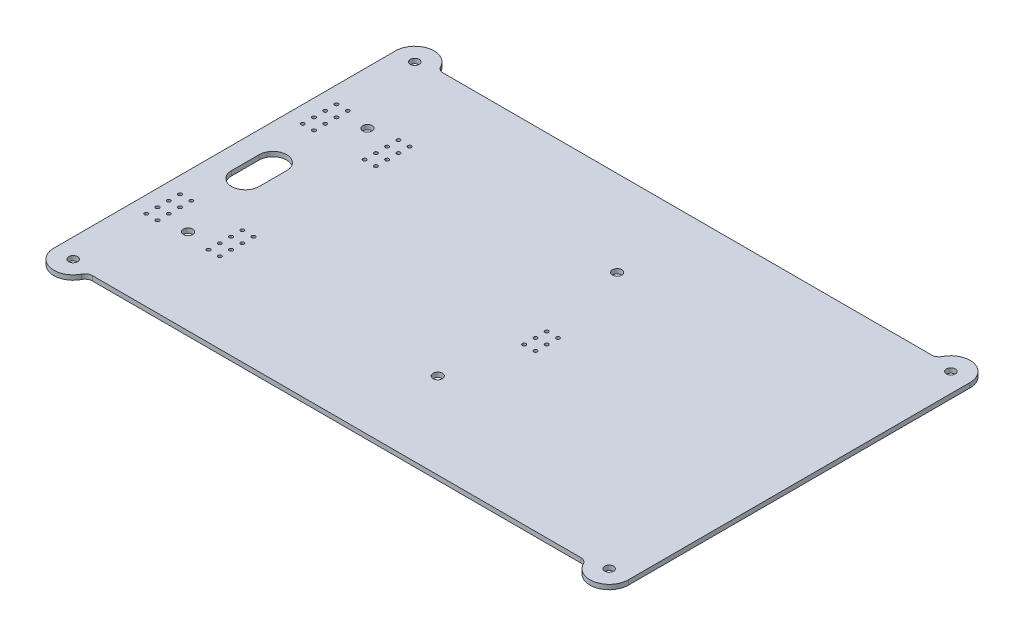
SolidWorks part; units mm, degrees
material "A-Glass Fiber"
ref_plane "Front Plane" through (0, 0, 0) normal (0, 0, 1) x (1, 0, 0)
ref_plane "Top Plane" through (0, 0, 0) normal (0, 1, 0) x (1, 0, 0)
ref_plane "Right Plane" through (0, 0, 0) normal (1, 0, 0) x (0, 0, -1)
sketch "Sketch1" plane through (0, 0, 0) normal (0, 1, 0) x (1, 0, 0)
  line L0 (0, 0) -> (135.8225, 0) construction
  line L2 (-58.612, -57.8231) -> (-58.612, 57.8231)
  line L4 (135.8225, -57.8231) -> (135.8225, 57.8231)
  line L7 (135.8225, 57.9501) -> (135.8225, 66.8401) construction
  line L8 (-44.0467, 59.3713) -> (121.2573, 59.3713)
  line L9 (-44.0467, -59.3713) -> (121.2573, -59.3713)
  arc A0 (-58.612, 57.8231) -> (-46.3123, 60.7627) centre (-52.1108, 57.8231) cw
  arc A1 (123.5228, 60.7627) -> (135.8225, 57.8231) centre (129.3214, 57.8231) cw
  arc A2 (135.8225, -57.8231) -> (123.5228, -60.7627) centre (129.3214, -57.8231) cw
  arc A3 (-46.3123, -60.7627) -> (-58.612, -57.8231) centre (-52.1108, -57.8231) cw
  arc A4 (-46.3123, -60.7627) -> (-44.0467, -59.3713) centre (-44.0467, -61.9113) cw
  arc A5 (121.2573, -59.3713) -> (123.5228, -60.7627) centre (121.2573, -61.9113) cw
  arc A6 (123.5228, 60.7627) -> (121.2573, 59.3713) centre (121.2573, 61.9113) cw
  arc A7 (-44.0467, 59.3713) -> (-46.3123, 60.7627) centre (-44.0467, 61.9113) cw
  arc A8 (31.0353, 66.8607) -> (46.1753, 66.8607) centre (38.6053, 66.9417) ccw construction
  circle A9 centre (-52.1108, -57.8231) radius 3.8735 construction
  circle A10 centre (129.3214, 57.8231) radius 3.8735 construction
  circle A11 centre (-52.1108, 57.8231) radius 3.8735 construction
  circle A12 centre (129.3214, -57.8231) radius 3.8735 construction
  point P1 (0, 0)
  dimension "D1" = 2.54
extrude "Boss-Extrude1" add sketch "Sketch1" against normal blind 1.5875
sketch "Sketch2" plane through (0, 0, 0) normal (0, 1, 0) x (1, 0, 0)
  circle A35 centre (-40.6725, -30.35) radius 1.5875
  circle A36 centre (-40.6725, -30.35) radius 1.5875
  circle A37 centre (-40.6725, 30.35) radius 1.5875
  circle A38 centre (-40.6725, 30.35) radius 1.5875
  circle A39 centre (43.8275, 30.35) radius 1.5875
  circle A40 centre (43.8275, 30.35) radius 1.5875
  circle A41 centre (43.8275, -30.35) radius 1.5875
  circle A42 centre (43.8275, -30.35) radius 1.5875
  dimension "D27" = 0
  dimension "D28" = 0
  dimension "D29" = 0
  dimension "D30" = 0
extrude "Cut-Extrude1" cut sketch "Sketch2" against normal through all
sketch "Sketch3" plane through (0, 0, 0) normal (0, 1, 0) x (1, 0, 0)
  line L5 (-46.6035, 4.285) -> (-46.6035, -5.035) construction
  line L6 (-41.9335, 4.285) -> (-41.9335, -5.035)
  line L7 (-51.2735, 4.285) -> (-51.2735, -5.035)
  line L17 (-43.2035, 3.375) -> (-41.9335, 3.375) construction
  line L18 (-44.8535, 7.2) -> (-44.1998, 8.2889) construction
  line L19 (-46.6035, 7.2) -> (-46.6035, 8.955) construction
  line L20 (-44.8535, 7.2) -> (-48.3535, 7.2) construction
  line L21 (-46.6035, -7.95) -> (-46.6035, -9.705) construction
  line L22 (-48.3535, -7.95) -> (-44.8535, -7.95) construction
  arc A13 (-41.9335, 4.285) -> (-51.2735, 4.285) centre (-46.6035, 4.285) ccw
  arc A14 (-51.2735, -5.035) -> (-41.9335, -5.035) centre (-46.6035, -5.035) ccw
  arc A17 (-44.8535, 0.46) -> (-44.8535, 6.29) centre (-46.6035, 3.375) ccw construction
  point P2 (-46.6035, -0.375)
  dimension "D1" = 1.27
extrude "Cut-Extrude2" cut sketch "Sketch3" against normal through all
sketch "Sketch4" plane through (0, -1.5875, 0) normal (0, -1, 0) x (1, 0, 0)
  line L4 (-34.35, -10.348) -> (-39.27, -10.348)
  line L5 (-34.35, -25.08) -> (-34.35, -10.348)
  line L6 (-39.27, -25.08) -> (-34.35, -25.08)
  line L7 (-39.27, -10.348) -> (-39.27, -25.08)
  line L8 (-34.35, -10.348) -> (-39.27, -10.348)
  line L9 (-34.35, -25.08) -> (-34.35, -10.348)
  line L10 (-39.27, -25.08) -> (-34.35, -25.08)
  line L11 (-39.27, -10.348) -> (-39.27, -25.08)
  line L12 (-34.35, 25.63) -> (-39.27, 25.63)
  line L13 (-34.35, 10.898) -> (-34.35, 25.63)
  line L14 (-39.27, 10.898) -> (-34.35, 10.898)
  line L15 (-39.27, 25.63) -> (-39.27, 10.898)
  line L16 (-34.35, 25.63) -> (-39.27, 25.63)
  line L17 (-34.35, 10.898) -> (-34.35, 25.63)
  line L18 (-39.27, 10.898) -> (-34.35, 10.898)
  line L19 (-39.27, 25.63) -> (-39.27, 10.898)
  line L20 (-44.42, 10.898) -> (-39.5, 10.898)
  line L21 (-39.5, 10.898) -> (-39.5, 25.63)
  line L22 (-39.5, 25.63) -> (-44.42, 25.63)
  line L23 (-44.42, 25.63) -> (-44.42, 10.898)
  line L24 (-44.42, 10.898) -> (-39.5, 10.898)
  line L25 (-39.5, 10.898) -> (-39.5, 25.63)
  line L26 (-39.5, 25.63) -> (-44.42, 25.63)
  line L27 (-44.42, 25.63) -> (-44.42, 10.898)
  line L28 (-39.5, -10.348) -> (-44.42, -10.348)
  line L29 (-39.5, -25.08) -> (-39.5, -10.348)
  line L30 (-44.42, -25.08) -> (-39.5, -25.08)
  line L31 (-44.42, -10.348) -> (-44.42, -25.08)
  line L32 (-39.5, -10.348) -> (-44.42, -10.348)
  line L33 (-39.5, -25.08) -> (-39.5, -10.348)
  line L34 (-44.42, -25.08) -> (-39.5, -25.08)
  line L35 (-44.42, -10.348) -> (-44.42, -25.08)
  line L36 (35.46, 13.148) -> (40.38, 13.148)
  line L37 (35.46, 27.88) -> (35.46, 13.148)
  line L38 (40.38, 27.88) -> (35.46, 27.88)
  line L39 (40.38, 13.148) -> (40.38, 27.88)
  line L40 (35.46, 13.148) -> (40.38, 13.148)
  line L41 (35.46, 27.88) -> (35.46, 13.148)
  line L42 (40.38, 27.88) -> (35.46, 27.88)
  line L43 (40.38, 13.148) -> (40.38, 27.88)
  dimension "D1" = 0
  dimension "D2" = 0
  dimension "D3" = 0
  dimension "D4" = 0
  dimension "D5" = 0
sketch "Sketch6" plane through (0, -1.5875, 0) normal (0, -1, 0) x (1, 0, 0)
  line L0 (-20.19, 27.65) -> (-20.19, 33.65) construction
  line L1 (-20.19, 33.65) -> (-14.19, 33.65) construction
  line L2 (-14.19, 33.65) -> (-14.19, 27.65) construction
  line L3 (-14.19, 27.65) -> (-20.19, 27.65) construction
  line L4 (33.69, -6.45) -> (33.69, -22.45)
  line L5 (54.59, -6.45) -> (33.69, -6.45)
  line L6 (54.59, -22.45) -> (54.59, -6.45)
  line L7 (33.69, -22.45) -> (54.59, -22.45)
  line L8 (33.69, -6.45) -> (33.69, -22.45)
  line L9 (54.59, -6.45) -> (33.69, -6.45)
  line L10 (54.59, -22.45) -> (54.59, -6.45)
  line L11 (33.69, -22.45) -> (54.59, -22.45)
  line L20 (-8.69, 27.65) -> (-8.69, 33.65) construction
  line L21 (-8.69, 33.65) -> (-2.69, 33.65) construction
  line L22 (-2.69, 33.65) -> (-2.69, 27.65) construction
  line L23 (-2.69, 27.65) -> (-8.69, 27.65) construction
  line L24 (-20.19, 27.65) -> (-20.19, 33.65)
  line L25 (-20.19, 33.65) -> (-14.19, 33.65)
  line L26 (-14.19, 33.65) -> (-14.19, 27.65)
  line L27 (-14.19, 27.65) -> (-20.19, 27.65)
  line L28 (-8.69, 27.65) -> (-8.69, 33.65)
  line L29 (-8.69, 33.65) -> (-2.69, 33.65)
  line L30 (-2.69, 33.65) -> (-2.69, 27.65)
  line L31 (-2.69, 27.65) -> (-8.69, 27.65)
  line L80 (55.31, -35.15) -> (55.31, 35.15)
  line L82 (55.31, 35.15) -> (-55.31, 35.15)
  line L84 (-55.31, 35.15) -> (-55.31, -35.15)
  line L86 (-55.31, -35.15) -> (55.31, -35.15)
  line L92 (55.31, -35.15) -> (55.31, 35.15)
  line L94 (55.31, 35.15) -> (-55.31, 35.15)
  line L96 (-55.31, 35.15) -> (-55.31, -35.15)
  line L98 (-55.31, -35.15) -> (55.31, -35.15)
  circle A0 centre (-17.19, 30.65) radius 1.75 construction
  circle A1 centre (-5.69, 30.65) radius 1.75 construction
  circle A2 centre (-17.19, 30.65) radius 1.75
  circle A3 centre (-5.69, 30.65) radius 1.75
  dimension "D1" = 0
  dimension "D2" = 0
sketch "Sketch7" plane through (0, -1.5875, 0) normal (0, -1, 0) x (1, 0, 0)
  circle A1 centre (49.2175, 6.483) radius 0.6
  circle A2 centre (49.2175, 6.483) radius 0.6
  circle A3 centre (-49.1085, -32.125) radius 0.6
  circle A4 centre (-49.1085, -32.125) radius 0.6
  circle A5 centre (-28.1535, -32.125) radius 0.6
  circle A6 centre (-28.1535, -32.125) radius 0.6
  circle A7 centre (-28.1535, 20.707) radius 0.6
  circle A8 centre (-28.1535, 20.707) radius 0.6
  circle A9 centre (-49.2355, 20.707) radius 0.6
  circle A10 centre (-49.2355, 20.707) radius 0.6
  circle A11 centre (-31.9635, 20.707) radius 0.6
  circle A12 centre (-31.9635, 20.707) radius 0.6
  circle A13 centre (-53.0455, 20.707) radius 0.6
  circle A14 centre (-53.0455, 20.707) radius 0.6
  circle A15 centre (-31.9635, 28.327) radius 0.6
  circle A16 centre (-31.9635, 28.327) radius 0.6
  circle A17 centre (-53.0455, 28.327) radius 0.6
  circle A18 centre (-53.0455, 28.327) radius 0.6
  circle A19 centre (-31.9635, 24.517) radius 0.6
  circle A20 centre (-31.9635, 24.517) radius 0.6
  circle A21 centre (-53.0455, 24.517) radius 0.6
  circle A22 centre (-53.0455, 24.517) radius 0.6
  circle A23 centre (-31.9635, -28.315) radius 0.6
  circle A24 centre (-31.9635, -28.315) radius 0.6
  circle A25 centre (-52.9185, -28.315) radius 0.6
  circle A26 centre (-52.9185, -28.315) radius 0.6
  circle A27 centre (-31.9635, -32.125) radius 0.6
  circle A28 centre (-31.9635, -32.125) radius 0.6
  circle A29 centre (-52.9185, -32.125) radius 0.6
  circle A30 centre (-52.9185, -32.125) radius 0.6
  circle A31 centre (-28.1535, 24.517) radius 0.6
  circle A32 centre (-28.1535, 24.517) radius 0.6
  circle A33 centre (-49.2355, 24.517) radius 0.6
  circle A34 centre (-49.2355, 24.517) radius 0.6
  circle A35 centre (-31.9635, 32.137) radius 0.6
  circle A36 centre (-31.9635, 32.137) radius 0.6
  circle A37 centre (-53.0455, 32.137) radius 0.6
  circle A38 centre (-53.0455, 32.137) radius 0.6
  circle A39 centre (-31.9635, -20.695) radius 0.6
  circle A40 centre (-31.9635, -20.695) radius 0.6
  circle A41 centre (-52.9185, -20.695) radius 0.6
  circle A42 centre (-52.9185, -20.695) radius 0.6
  circle A43 centre (-31.9635, -24.505) radius 0.6
  circle A44 centre (-31.9635, -24.505) radius 0.6
  circle A45 centre (-52.9185, -24.505) radius 0.6
  circle A46 centre (-52.9185, -24.505) radius 0.6
  circle A47 centre (-28.1535, 32.137) radius 0.6
  circle A48 centre (-28.1535, 32.137) radius 0.6
  circle A49 centre (-49.2355, 32.137) radius 0.6
  circle A50 centre (-49.2355, 32.137) radius 0.6
  circle A51 centre (-28.1535, 28.327) radius 0.6
  circle A52 centre (-28.1535, 28.327) radius 0.6
  circle A53 centre (-49.2355, 28.327) radius 0.6
  circle A54 centre (-49.2355, 28.327) radius 0.6
  circle A55 centre (-28.1535, -24.505) radius 0.6
  circle A56 centre (-28.1535, -24.505) radius 0.6
  circle A57 centre (-49.1085, -24.505) radius 0.6
  circle A58 centre (-49.1085, -24.505) radius 0.6
  circle A59 centre (-28.1535, -28.315) radius 0.6
  circle A60 centre (-28.1535, -28.315) radius 0.6
  circle A61 centre (-49.1085, -28.315) radius 0.6
  circle A62 centre (-49.1085, -28.315) radius 0.6
  circle A63 centre (49.2175, 2.673) radius 0.6
  circle A64 centre (49.2175, 2.673) radius 0.6
  circle A65 centre (53.0275, -1.137) radius 0.6
  circle A66 centre (53.0275, -1.137) radius 0.6
  circle A67 centre (53.0275, 2.673) radius 0.6
  circle A68 centre (53.0275, 2.673) radius 0.6
  circle A69 centre (53.0275, 6.483) radius 0.6
  circle A70 centre (53.0275, 6.483) radius 0.6
  circle A71 centre (-28.1535, -20.695) radius 0.6
  circle A72 centre (-28.1535, -20.695) radius 0.6
  circle A73 centre (-49.1085, -20.695) radius 0.6
  circle A74 centre (-49.1085, -20.695) radius 0.6
  circle A75 centre (49.2175, -1.137) radius 0.6
  circle A76 centre (49.2175, -1.137) radius 0.6
  dimension "D1" = 0
  dimension "D2" = 0
  dimension "D3" = 0
  dimension "D4" = 0
  dimension "D5" = 0
  dimension "D6" = 0
  dimension "D7" = 0
  dimension "D8" = 0
  dimension "D9" = 0
  dimension "D10" = 0
  dimension "D11" = 0
  dimension "D12" = 0
  dimension "D13" = 0
  dimension "D14" = 0
  dimension "D15" = 0
  dimension "D16" = 0
  dimension "D17" = 0
  dimension "D18" = 0
  dimension "D19" = 0
  dimension "D20" = 0
  dimension "D21" = 0
  dimension "D22" = 0
  dimension "D23" = 0
  dimension "D24" = 0
  dimension "D25" = 0
  dimension "D26" = 0
  dimension "D27" = 0
  dimension "D28" = 0
  dimension "D29" = 0
  dimension "D30" = 0
  dimension "D31" = 0
  dimension "D32" = 0
  dimension "D33" = 0
  dimension "D34" = 0
  dimension "D35" = 0
  dimension "D36" = 0
  dimension "D37" = 0
  dimension "D38" = 0
extrude "Cut-Extrude3" cut sketch "Sketch7" against normal through all
sketch "Sketch8" plane through (0, -1.5875, 0) normal (0, -1, 0) x (1, 0, 0)
  line L4 (-47.9085, -18.395) -> (-54.7585, -18.395)
  line L5 (-47.9085, -34.425) -> (-47.9085, -18.395)
  line L6 (-54.7585, -34.425) -> (-47.9085, -34.425)
  line L7 (-54.7585, -18.395) -> (-54.7585, -34.425)
  line L8 (-47.9085, -18.395) -> (-54.7585, -18.395)
  line L9 (-47.9085, -34.425) -> (-47.9085, -18.395)
  line L10 (-54.7585, -34.425) -> (-47.9085, -34.425)
  line L11 (-54.7585, -18.395) -> (-54.7585, -34.425)
  line L12 (-54.8855, 18.407) -> (-48.0355, 18.407)
  line L13 (-48.0355, 18.407) -> (-48.0355, 34.437)
  line L14 (-48.0355, 34.437) -> (-54.8855, 34.437)
  line L15 (-54.8855, 34.437) -> (-54.8855, 18.407)
  line L16 (-54.8855, 18.407) -> (-48.0355, 18.407)
  line L17 (-48.0355, 18.407) -> (-48.0355, 34.437)
  line L18 (-48.0355, 34.437) -> (-54.8855, 34.437)
  line L19 (-54.8855, 34.437) -> (-54.8855, 18.407)
  line L20 (-33.8035, -18.395) -> (-33.8035, -34.425)
  line L21 (-33.8035, -34.425) -> (-26.9535, -34.425)
  line L22 (-26.9535, -34.425) -> (-26.9535, -18.395)
  line L23 (-26.9535, -18.395) -> (-33.8035, -18.395)
  line L24 (-33.8035, -18.395) -> (-33.8035, -34.425)
  line L25 (-33.8035, -34.425) -> (-26.9535, -34.425)
  line L26 (-26.9535, -34.425) -> (-26.9535, -18.395)
  line L27 (-26.9535, -18.395) -> (-33.8035, -18.395)
  line L28 (-26.9535, 34.437) -> (-33.8035, 34.437)
  line L29 (-26.9535, 18.407) -> (-26.9535, 34.437)
  line L30 (-33.8035, 18.407) -> (-26.9535, 18.407)
  line L31 (-33.8035, 34.437) -> (-33.8035, 18.407)
  line L32 (-26.9535, 34.437) -> (-33.8035, 34.437)
  line L33 (-26.9535, 18.407) -> (-26.9535, 34.437)
  line L34 (-33.8035, 18.407) -> (-26.9535, 18.407)
  line L35 (-33.8035, 34.437) -> (-33.8035, 18.407)
  line L36 (47.8175, 8.783) -> (47.8175, -3.437)
  line L37 (47.8175, -3.437) -> (54.6675, -3.437)
  line L38 (54.6675, -3.437) -> (54.6675, 8.783)
  line L39 (54.6675, 8.783) -> (47.8175, 8.783)
  line L40 (47.8175, 8.783) -> (47.8175, -3.437)
  line L41 (47.8175, -3.437) -> (54.6675, -3.437)
  line L42 (54.6675, -3.437) -> (54.6675, 8.783)
  line L43 (54.6675, 8.783) -> (47.8175, 8.783)
  dimension "D1" = 0
  dimension "D2" = 0
  dimension "D3" = 0
  dimension "D4" = 0
  dimension "D5" = 0
sketch "Sketch9" plane through (0, 0, 0) normal (0, 1, 0) x (1, 0, 0)
  circle A0 centre (-52.1108, 57.8231) radius 1.5
  circle A1 centre (-52.1108, -57.8231) radius 1.5
  circle A2 centre (129.3214, 57.8231) radius 1.5
  circle A3 centre (129.3214, -57.8231) radius 1.5
  point P2 (-52.1108, -57.8231)
  point P5 (129.3214, -57.8231)
  point P8 (129.3214, 57.8231)
  point P11 (-52.9737, 59.4827)
  point P12 (-52.1108, 57.8231)
  dimension "D1" = 3
extrude "Cut-Extrude4" cut sketch "Sketch9" against normal through all
sketch "Sketch11" plane through (0, -1.5875, 0) normal (0, -1, 0) x (1, 0, 0)
  line L0 (140.0242, 31.6837) -> (152.7242, 31.6837) construction
  line L1 (140.0242, 31.6837) -> (152.7242, 31.6837)
sketch "Sketch12" plane through (0, -1.5875, 0) normal (0, -1, 0) x (1, 0, 0)
  circle A0 centre (-40.6725, -30.35) radius 3.81
  circle A1 centre (-40.6725, -30.35) radius 1.5875 construction
  circle A2 centre (-40.6725, 30.35) radius 3.81
  circle A3 centre (43.8275, 30.35) radius 3.81
  circle A4 centre (43.8275, -30.35) radius 3.81
  dimension "D1" = 7.62
sketch "Sketch14" plane through (0, -1.5875, 0) normal (0, -1, 0) x (1, 0, 0)
  line L3 (125.6585, 59.0931) -> (123.9874, 59.0931)
  line L4 (123.9874, 59.0931) -> (123.9874, 56.5531)
  line L5 (123.9874, 56.5531) -> (125.6585, 56.5531)
  line L6 (125.6585, 59.0931) -> (123.9874, 59.0931)
  line L7 (123.9874, 59.0931) -> (123.9874, 56.5531)
  line L8 (123.9874, 56.5531) -> (125.6585, 56.5531)
  line L9 (132.9843, 56.5531) -> (134.6554, 56.5531)
  line L10 (134.6554, 56.5531) -> (134.6554, 59.0931)
  line L11 (134.6554, 59.0931) -> (132.9843, 59.0931)
  line L12 (132.9843, 56.5531) -> (134.6554, 56.5531)
  line L13 (134.6554, 56.5531) -> (134.6554, 59.0931)
  line L14 (134.6554, 59.0931) -> (132.9843, 59.0931)
  line L15 (128.0514, 54.1602) -> (128.0514, 52.4891)
  line L16 (128.0514, 52.4891) -> (130.5914, 52.4891)
  line L17 (130.5914, 52.4891) -> (130.5914, 54.1602)
  line L18 (128.0514, 54.1602) -> (128.0514, 52.4891)
  line L19 (128.0514, 52.4891) -> (130.5914, 52.4891)
  line L20 (130.5914, 52.4891) -> (130.5914, 54.1602)
  line L21 (125.6585, -56.5531) -> (123.9874, -56.5531)
  line L22 (123.9874, -56.5531) -> (123.9874, -59.0931)
  line L23 (123.9874, -59.0931) -> (125.6585, -59.0931)
  line L24 (125.6585, -56.5531) -> (123.9874, -56.5531)
  line L25 (123.9874, -56.5531) -> (123.9874, -59.0931)
  line L26 (123.9874, -59.0931) -> (125.6585, -59.0931)
  line L27 (130.5914, 63.1571) -> (128.0514, 63.1571)
  line L28 (128.0514, 63.1571) -> (128.0514, 61.486)
  line L29 (130.5914, 61.486) -> (130.5914, 63.1571)
  line L30 (130.5914, 63.1571) -> (128.0514, 63.1571)
  line L31 (128.0514, 63.1571) -> (128.0514, 61.486)
  line L32 (130.5914, 61.486) -> (130.5914, 63.1571)
  line L33 (130.5914, -54.1602) -> (130.5914, -52.4891)
  line L34 (130.5914, -52.4891) -> (128.0514, -52.4891)
  line L35 (128.0514, -52.4891) -> (128.0514, -54.1602)
  line L36 (130.5914, -54.1602) -> (130.5914, -52.4891)
  line L37 (130.5914, -52.4891) -> (128.0514, -52.4891)
  line L38 (128.0514, -52.4891) -> (128.0514, -54.1602)
  line L39 (128.0514, -61.486) -> (128.0514, -63.1571)
  line L40 (128.0514, -63.1571) -> (130.5914, -63.1571)
  line L41 (130.5914, -63.1571) -> (130.5914, -61.486)
  line L42 (128.0514, -61.486) -> (128.0514, -63.1571)
  line L43 (128.0514, -63.1571) -> (130.5914, -63.1571)
  line L44 (130.5914, -63.1571) -> (130.5914, -61.486)
  line L45 (134.6554, -59.0931) -> (134.6554, -56.5531)
  line L46 (132.9843, -59.0931) -> (134.6554, -59.0931)
  line L47 (134.6554, -56.5531) -> (132.9843, -56.5531)
  line L48 (134.6554, -59.0931) -> (134.6554, -56.5531)
  line L49 (132.9843, -59.0931) -> (134.6554, -59.0931)
  line L50 (134.6554, -56.5531) -> (132.9843, -56.5531)
  line L51 (-55.7737, -56.5531) -> (-57.4448, -56.5531)
  line L52 (-57.4448, -56.5531) -> (-57.4448, -59.0931)
  line L53 (-57.4448, -59.0931) -> (-55.7737, -59.0931)
  line L54 (-55.7737, -56.5531) -> (-57.4448, -56.5531)
  line L55 (-57.4448, -56.5531) -> (-57.4448, -59.0931)
  line L56 (-57.4448, -59.0931) -> (-55.7737, -59.0931)
  line L57 (-48.4479, -59.0931) -> (-46.7768, -59.0931)
  line L58 (-46.7768, -59.0931) -> (-46.7768, -56.5531)
  line L59 (-46.7768, -56.5531) -> (-48.4479, -56.5531)
  line L60 (-48.4479, -59.0931) -> (-46.7768, -59.0931)
  line L61 (-46.7768, -59.0931) -> (-46.7768, -56.5531)
  line L62 (-46.7768, -56.5531) -> (-48.4479, -56.5531)
  line L63 (-53.3808, -63.1571) -> (-50.8408, -63.1571)
  line L64 (-50.8408, -63.1571) -> (-50.8408, -61.486)
  line L65 (-53.3808, -61.486) -> (-53.3808, -63.1571)
  line L66 (-53.3808, -63.1571) -> (-50.8408, -63.1571)
  line L67 (-50.8408, -63.1571) -> (-50.8408, -61.486)
  line L68 (-53.3808, -61.486) -> (-53.3808, -63.1571)
  line L69 (-50.8408, -54.1602) -> (-50.8408, -52.4891)
  line L70 (-50.8408, -52.4891) -> (-53.3808, -52.4891)
  line L71 (-53.3808, -52.4891) -> (-53.3808, -54.1602)
  line L72 (-50.8408, -54.1602) -> (-50.8408, -52.4891)
  line L73 (-50.8408, -52.4891) -> (-53.3808, -52.4891)
  line L74 (-53.3808, -52.4891) -> (-53.3808, -54.1602)
  line L75 (-50.8408, 61.486) -> (-50.8408, 63.1571)
  line L76 (-50.8408, 63.1571) -> (-53.3808, 63.1571)
  line L77 (-53.3808, 63.1571) -> (-53.3808, 61.486)
  line L78 (-50.8408, 61.486) -> (-50.8408, 63.1571)
  line L79 (-50.8408, 63.1571) -> (-53.3808, 63.1571)
  line L80 (-53.3808, 63.1571) -> (-53.3808, 61.486)
  line L81 (-46.7768, 56.5531) -> (-46.7768, 59.0931)
  line L82 (-48.4479, 56.5531) -> (-46.7768, 56.5531)
  line L83 (-46.7768, 59.0931) -> (-48.4479, 59.0931)
  line L84 (-46.7768, 56.5531) -> (-46.7768, 59.0931)
  line L85 (-48.4479, 56.5531) -> (-46.7768, 56.5531)
  line L86 (-46.7768, 59.0931) -> (-48.4479, 59.0931)
  line L87 (-53.3808, 54.1602) -> (-53.3808, 52.4891)
  line L88 (-53.3808, 52.4891) -> (-50.8408, 52.4891)
  line L89 (-50.8408, 52.4891) -> (-50.8408, 54.1602)
  line L90 (-53.3808, 54.1602) -> (-53.3808, 52.4891)
  line L91 (-53.3808, 52.4891) -> (-50.8408, 52.4891)
  line L92 (-50.8408, 52.4891) -> (-50.8408, 54.1602)
  line L93 (-57.4448, 59.0931) -> (-57.4448, 56.5531)
  line L94 (-57.4448, 56.5531) -> (-55.7737, 56.5531)
  line L95 (-55.7737, 59.0931) -> (-57.4448, 59.0931)
  line L96 (-57.4448, 59.0931) -> (-57.4448, 56.5531)
  line L97 (-57.4448, 56.5531) -> (-55.7737, 56.5531)
  line L98 (-55.7737, 59.0931) -> (-57.4448, 59.0931)
  circle A1 centre (-44.2368, 19.5199) radius 3.8735
  circle A2 centre (-44.2368, 19.5199) radius 3.8735
  circle A3 centre (-44.2368, -19.5199) radius 3.8735
  circle A4 centre (-44.2368, -19.5199) radius 3.8735
  circle A5 centre (121.4474, -19.5199) radius 3.8735
  circle A6 centre (121.4474, -19.5199) radius 3.8735
  circle A7 centre (121.4474, 19.5199) radius 3.8735
  circle A8 centre (121.4474, 19.5199) radius 3.8735
  circle A9 centre (129.3214, -57.8231) radius 3.8735
  circle A10 centre (129.3214, -57.8231) radius 3.8735
  circle A11 centre (129.3214, 57.8231) radius 3.8735
  circle A12 centre (129.3214, 57.8231) radius 3.8735
  arc A13 (125.6585, 59.0931) -> (125.6585, 56.5531) centre (129.3214, 57.8231) ccw
  arc A14 (125.6585, 59.0931) -> (125.6585, 56.5531) centre (129.3214, 57.8231) ccw
  arc A15 (132.9843, 56.5531) -> (132.9843, 59.0931) centre (129.3214, 57.8231) ccw
  arc A16 (132.9843, 56.5531) -> (132.9843, 59.0931) centre (129.3214, 57.8231) ccw
  circle A17 centre (-52.1108, 57.8231) radius 3.8735
  circle A18 centre (-52.1108, 57.8231) radius 3.8735
  circle A19 centre (-52.1108, -57.8231) radius 3.8735
  circle A20 centre (-52.1108, -57.8231) radius 3.8735
  arc A21 (128.0514, 54.1602) -> (130.5914, 54.1602) centre (129.3214, 57.8231) ccw
  arc A22 (128.0514, 54.1602) -> (130.5914, 54.1602) centre (129.3214, 57.8231) ccw
  arc A23 (125.6585, -56.5531) -> (125.6585, -59.0931) centre (129.3214, -57.8231) ccw
  arc A24 (125.6585, -56.5531) -> (125.6585, -59.0931) centre (129.3214, -57.8231) ccw
  arc A25 (130.5914, 61.486) -> (128.0514, 61.486) centre (129.3214, 57.8231) ccw
  arc A26 (130.5914, 61.486) -> (128.0514, 61.486) centre (129.3214, 57.8231) ccw
  arc A27 (130.5914, -54.1602) -> (128.0514, -54.1602) centre (129.3214, -57.8231) ccw
  arc A28 (130.5914, -54.1602) -> (128.0514, -54.1602) centre (129.3214, -57.8231) ccw
  arc A29 (128.0514, -61.486) -> (130.5914, -61.486) centre (129.3214, -57.8231) ccw
  arc A30 (128.0514, -61.486) -> (130.5914, -61.486) centre (129.3214, -57.8231) ccw
  arc A31 (132.9843, -59.0931) -> (132.9843, -56.5531) centre (129.3214, -57.8231) ccw
  arc A32 (132.9843, -59.0931) -> (132.9843, -56.5531) centre (129.3214, -57.8231) ccw
  arc A33 (-55.7737, -56.5531) -> (-55.7737, -59.0931) centre (-52.1108, -57.8231) ccw
  arc A34 (-55.7737, -56.5531) -> (-55.7737, -59.0931) centre (-52.1108, -57.8231) ccw
  arc A35 (-48.4479, -59.0931) -> (-48.4479, -56.5531) centre (-52.1108, -57.8231) ccw
  arc A36 (-48.4479, -59.0931) -> (-48.4479, -56.5531) centre (-52.1108, -57.8231) ccw
  arc A37 (-53.3808, -61.486) -> (-50.8408, -61.486) centre (-52.1108, -57.8231) ccw
  arc A38 (-53.3808, -61.486) -> (-50.8408, -61.486) centre (-52.1108, -57.8231) ccw
  arc A39 (-50.8408, -54.1602) -> (-53.3808, -54.1602) centre (-52.1108, -57.8231) ccw
  arc A40 (-50.8408, -54.1602) -> (-53.3808, -54.1602) centre (-52.1108, -57.8231) ccw
  arc A41 (-50.8408, 61.486) -> (-53.3808, 61.486) centre (-52.1108, 57.8231) ccw
  arc A42 (-50.8408, 61.486) -> (-53.3808, 61.486) centre (-52.1108, 57.8231) ccw
  arc A43 (-48.4479, 56.5531) -> (-48.4479, 59.0931) centre (-52.1108, 57.8231) ccw
  arc A44 (-48.4479, 56.5531) -> (-48.4479, 59.0931) centre (-52.1108, 57.8231) ccw
  arc A45 (-53.3808, 54.1602) -> (-50.8408, 54.1602) centre (-52.1108, 57.8231) ccw
  arc A46 (-53.3808, 54.1602) -> (-50.8408, 54.1602) centre (-52.1108, 57.8231) ccw
  arc A47 (-55.7737, 59.0931) -> (-55.7737, 56.5531) centre (-52.1108, 57.8231) ccw
  arc A48 (-55.7737, 59.0931) -> (-55.7737, 56.5531) centre (-52.1108, 57.8231) ccw
  dimension "D1" = 0
  dimension "D2" = 0
  dimension "D3" = 0
  dimension "D4" = 0
  dimension "D5" = 0
  dimension "D6" = 0
  dimension "D7" = 0
  dimension "D8" = 0
  dimension "D9" = 0
  dimension "D10" = 0
  dimension "D11" = 0
  dimension "D12" = 0
  dimension "D13" = 0
  dimension "D14" = 0
  dimension "D15" = 0
  dimension "D16" = 0
  dimension "D17" = 0
  dimension "D18" = 0
  dimension "D19" = 0
  dimension "D20" = 0
  dimension "D21" = 0
  dimension "D22" = 0
  dimension "D23" = 0
  dimension "D24" = 0
equation "\"62.5mi\"=0.1"
